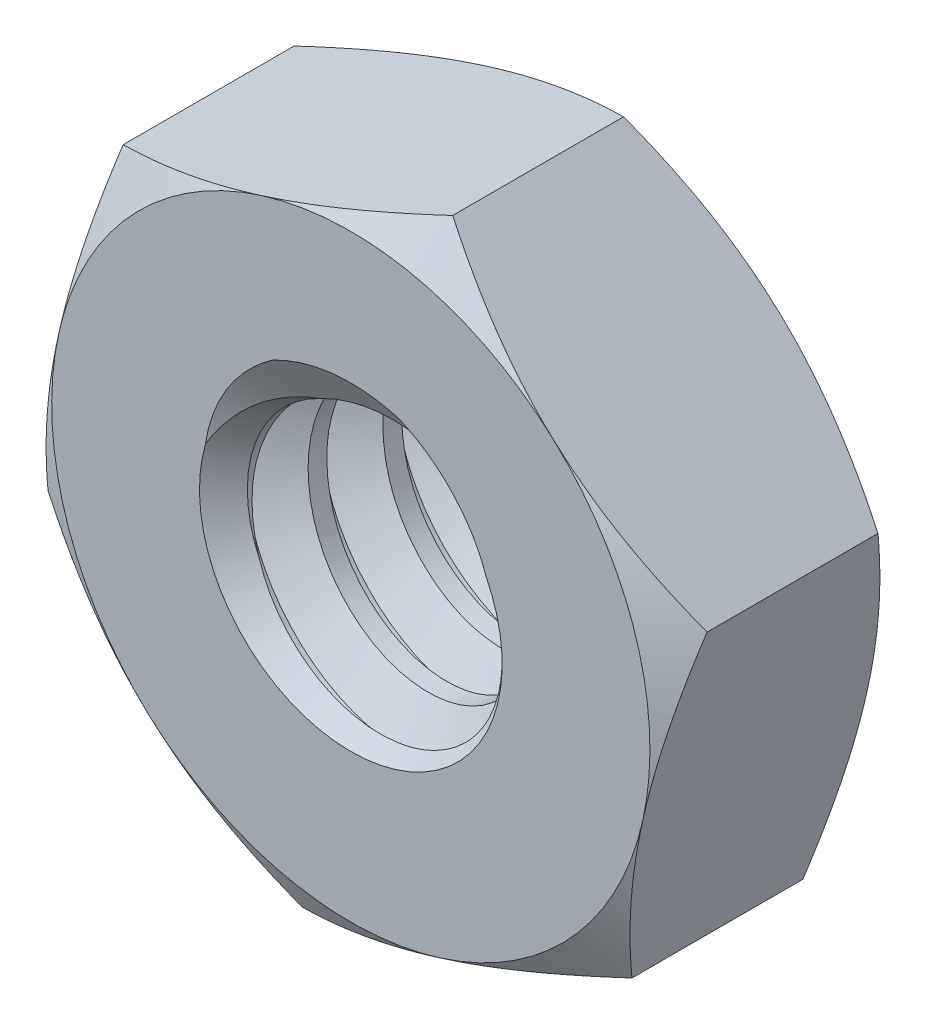
SolidWorks part; units mm, degrees
ref_plane "Front Plane" through (0, 0, 0) normal (0, 0, 1) x (1, 0, 0)
ref_plane "Top Plane" through (0, 0, 0) normal (0, 1, 0) x (1, 0, 0)
ref_plane "Right Plane" through (0, 0, 0) normal (1, 0, 0) x (0, 0, -1)
sketch "Sketch1" plane through (0, 0, 0) normal (0, 0, 1) x (1, 0, 0)
  line L1 (2.7, -2.4801) -> (3.4978, 1.0982)
  line L2 (3.4978, 1.0982) -> (0.7978, 3.5783)
  line L3 (0.7978, 3.5783) -> (-2.7, 2.4801)
  line L4 (-2.7, 2.4801) -> (-3.4978, -1.0982)
  line L5 (-3.4978, -1.0982) -> (-0.7978, -3.5783)
  line L6 (-0.7978, -3.5783) -> (2.7, -2.4801)
  circle A0 centre (0, 0) radius 3.175 construction
  dimension "D1" = 6.35
  dimension "D2" = 0.7978
extrude "Boss-Extrude1" add sketch "Sketch1" along normal blind 2.3813
hole_wizard "Tap Drill for #6-32 Tap1" positions "Sketch15" profile "Sketch16" hole size "#6-32" standard "ANSI Inch" end condition through all
sketch "Sketch15" plane through (0, 0, 0) normal (0, 0, -1) x (-1, 0, 0)
  point P0 (0, 0)
sketch "Sketch16" plane through (0, 0, 0) normal (1, 0, 0) x (0, 1, 0)
  line L0 (0, 0) -> (0, 2.3813)
  line L1 (0, 2.3813) -> (1.3525, 2.3813)
  line L2 (1.3525, 2.3813) -> (1.3525, 0)
  line L5 (1.3525, 0) -> (0, 0)
  line L11 (0, -6.35) -> (0, 107.95) construction
  dimension "Thru Hole Dia." = 2.7051
  dimension "Thru Hole Depth" = 2.3813
sketch "Sketch13" plane through (0, 0, 0) normal (0, 0, -1) x (-1, 0, 0)
  circle A0 centre (0, 0) radius 3.175
  dimension "D1" = 6.35
extrude "Cut-Extrude2" cut sketch "Sketch13" against normal blind 2.3813 draft 60 flip side to cut
sketch "Sketch14" plane through (0, 0, 2.3813) normal (0, 0, 1) x (1, 0, 0)
  line L0 (0, 0) -> (0.7978, 3.5783) construction
  circle A0 centre (0, 0) radius 3.175
  dimension "D1" = 6.35
extrude "Cut-Extrude3" cut sketch "Sketch14" against normal blind 2.3813 draft 60 flip side to cut
chamfer "Chamfer1" distance 0.254 angle 45 2 edges at (-1.3525, 0, 2.3813) (-1.3525, 0, 0)
thread "Thread1" pitch 0.7937 method cut profile "Thread Profile1" start angle 0, offset 0.762, length 0, pitch 0.7937, diameter 2.7051
ref_plane "Plane1" through (1.3525, 0, -0.508) normal (0, -1, 0) x (1, 0, 0)
sketch "Thread Profile1" plane through (1.3525, 0, -0.508) normal (0, -1, 0) x (1, 0, 0)
  line L0 (0, 0) -> (0, 0.7937) construction
  line L1 (0, 0) -> (0.4296, 0.248)
  line L2 (0.4296, 0.248) -> (0.4296, 0.3473)
  line L3 (0.4296, 0.3473) -> (0, 0.5953)
  line L4 (0.4296, 0.2977) -> (0, 0.2977) construction
  line L11 (0, 0) -> (0, 0.5953)
  point P2 (0, 0)
  dimension "Pitch" = 0.7937
  dimension "Profile_Angle" = 60
  dimension "Profile_Land" = 0.0992
  dimension "Profile_Height" = 0.4296
